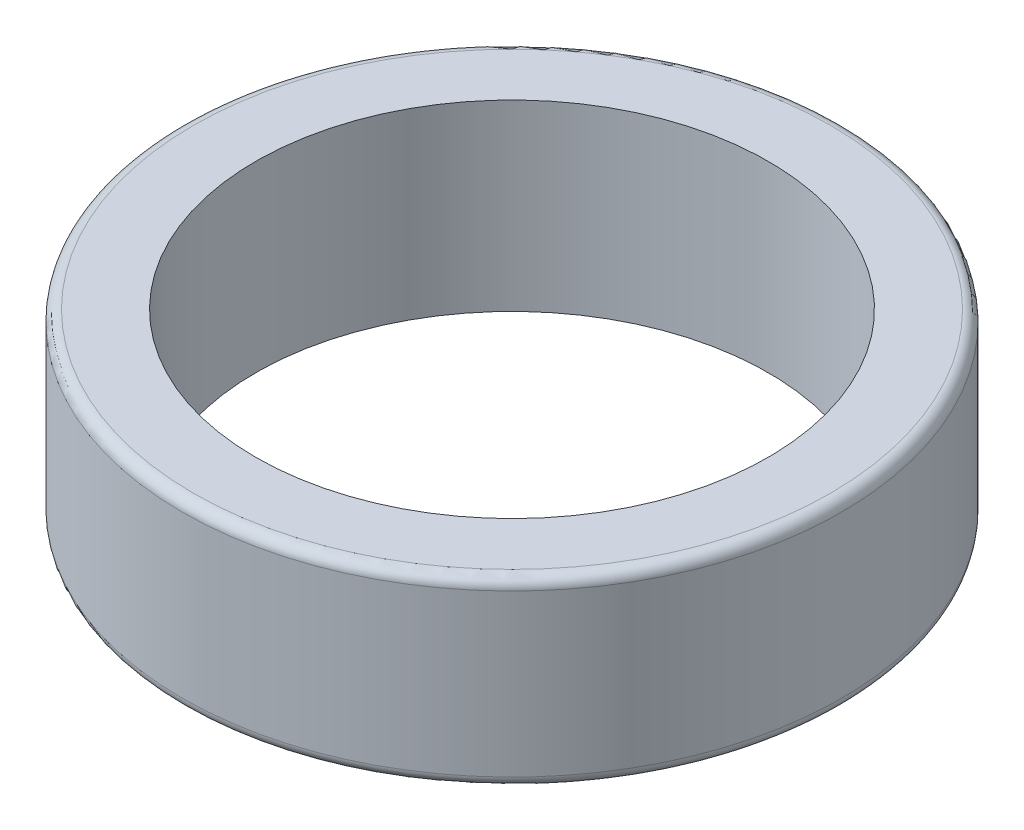
SolidWorks part; units mm, degrees
ref_plane "Front Plane" through (0, 0, 0) normal (0, 0, 1) x (1, 0, 0)
ref_plane "Top Plane" through (0, 0, 0) normal (0, 1, 0) x (1, 0, 0)
ref_plane "Right Plane" through (0, 0, 0) normal (1, 0, 0) x (0, 0, -1)
sketch "Sketch1" plane through (0, 0, 0) normal (0, 1, 0) x (1, 0, 0)
  circle A0 centre (0, 0) radius 70
  circle A1 centre (0, 0) radius 90
  dimension "D1" = 140
  dimension "D2" = 180
extrude "Boss-Extrude1" add sketch "Sketch1" along normal blind 25 and the other way blind 25
fillet "Fillet1" radius 3 2 edges at (0, 25, 90) (0, -25, 90)
